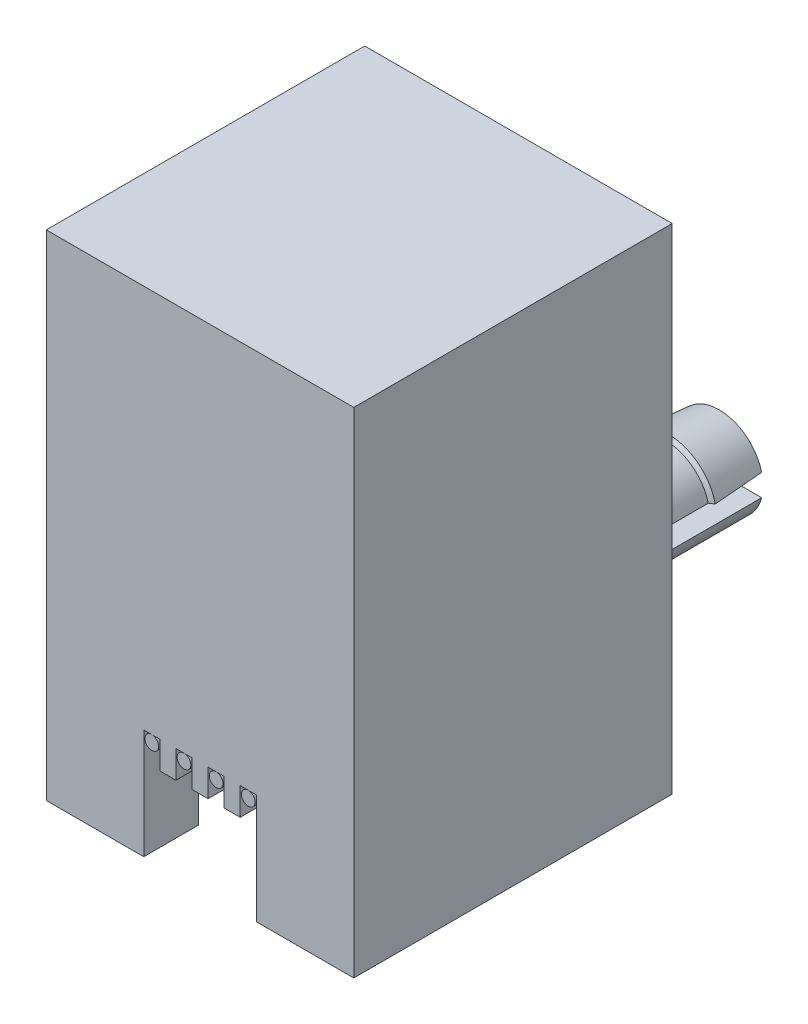
SolidWorks part; units mm, degrees
material "ABS PC"
ref_plane "Front Plane" through (0, 0, 0) normal (0, 0, 1) x (1, 0, 0)
ref_plane "Top Plane" through (0, 0, 0) normal (0, 1, 0) x (1, 0, 0)
ref_plane "Right Plane" through (0, 0, 0) normal (1, 0, 0) x (0, 0, -1)
sketch "Sketch1" plane through (0, 0, 0) normal (0, 1, 0) x (1, 0, 0)
  line L0 (5.6, -5.8) -> (5.6, 5.8)
  line L1 (-5.6, -5.8) -> (5.6, -5.8)
  line L2 (-5.6, -5.8) -> (-5.6, 5.8)
  line L3 (5.6, 5.8) -> (-5.6, 5.8)
  line L4 (-5.6, 0) -> (5.6, 0) construction
  line L5 (0, 5.8) -> (0, -5.8) construction
  dimension "D1" = 11.2
  dimension "D2" = 11.6
extrude "Extrude1" add sketch "Sketch1" along normal mid plane 18
sketch "Sketch2" plane through (0, -9, 0) normal (0, -1, 0) x (1, 0, 0)
  line L0 (-5.6, 5.8) -> (5.6, 5.8) construction
  line L1 (4, 3.8) -> (-4, 3.8)
  line L2 (4, -3) -> (4, 3.8)
  line L3 (4, -3) -> (2.9, -3)
  line L4 (2.9, -4.8) -> (2.9, -3)
  line L5 (2.9, -4.8) -> (-2.9, -4.8)
  line L6 (5.6, -5.8) -> (-5.6, -5.8) construction
  line L7 (0, -5.8) -> (0, 5.8) construction
  line L11 (-2.9, -4.8) -> (-2.9, -3)
  line L12 (-4, -3) -> (-2.9, -3)
  line L13 (-4, -3) -> (-4, 3.8)
  dimension "D1" = 2
  dimension "D2" = 8
  dimension "D4" = 6.8
  dimension "D5" = 1.1
  dimension "D6" = 1.8
extrude "Cut-Extrude1" cut sketch "Sketch2" against normal blind 10
sketch "Sketch3" plane through (0, 0, 5.8) normal (0, 0, 1) x (1, 0, 0)
  line L0 (-2.05, -9) -> (-2.05, -6)
  line L1 (-2.05, -6) -> (2.05, -6)
  line L2 (2.05, -6) -> (2.05, -9)
  line L3 (2.05, -9) -> (-2.05, -9)
  line L4 (0, -9) -> (0, -6) construction
  line L5 (-5.6, -9) -> (5.6, -9) construction
  dimension "D1" = 4.1
  dimension "D2" = 3
extrude "Cut-Extrude2" cut sketch "Sketch3" against normal up to surface (2 mm away) up to face at (0, -4, 3.8)
sketch "Sketch4" plane through (0, 0, -5.8) normal (0, 0, -1) x (-1, 0, 0)
  line L0 (1.5, -7.2) -> (1.5, -9)
  line L1 (2.9, -7.2) -> (1.5, -7.2)
  line L2 (2.9, -4.2) -> (2.9, -7.2)
  line L3 (-2.9, -4.2) -> (2.9, -4.2)
  line L4 (-2.9, -7.2) -> (-2.9, -4.2)
  line L5 (-1.5, -7.2) -> (-2.9, -7.2)
  line L6 (-1.5, -9) -> (-1.5, -7.2)
  line L7 (1.5, -9) -> (-1.5, -9)
  line L8 (0, -9) -> (0, -4.2) construction
  line L9 (-5.6, -9) -> (5.6, -9) construction
  dimension "D1" = 5.8
  dimension "D2" = 3
  dimension "D3" = 1.8
  dimension "D4" = 3
extrude "Cut-Extrude3" cut sketch "Sketch4" against normal up to surface (1 mm away) up to face at (0, -4, -4.8)
sketch "Sketch5" plane through (0, 0, -5.8) normal (0, 0, -1) x (-1, 0, 0)
  line L4 (-5.6, -9) -> (-1.5, -9) construction
  line L5 (-5.6, 9) -> (-5.6, -9) construction
  line L6 (-5.41, -1.12) -> (-2.21, -1.12) construction
  line L7 (-5.3592, -1.52) -> (-2.2608, -1.52)
  line L8 (-5.3592, -0.72) -> (-2.2608, -0.72)
  line L9 (-5.41, -0.72) -> (-2.21, -0.72) construction
  line L10 (-5.41, -1.52) -> (-2.21, -1.52) construction
  arc A1 (-5.3592, -1.52) -> (-2.2608, -1.52) centre (-3.81, -1.12) ccw
  arc A2 (-2.2608, -0.72) -> (-5.3592, -0.72) centre (-3.81, -1.12) ccw
  dimension "D2" = 3.2
  dimension "D3" = 7.88
  dimension "D5" = 1.79
  dimension "D6" = 0.4
  dimension "D7" = 0.4
extrude "Extrude2" add sketch "Sketch5" along normal blind 3.5
ref_plane "Plane1" through (0, 0, -7.4537) normal (0, 0, -1) x (-1, 0, 0)
sketch "Sketch6" plane through (0, 0, -7.4537) normal (0, 0, -1) x (-1, 0, 0)
  line L1 (-5.3592, -0.72) -> (-2.2608, -0.72) construction
  line L2 (-5.5137, -0.72) -> (-2.1063, -0.72)
  arc A0 (-2.1063, -0.72) -> (-5.5137, -0.72) centre (-3.81, -1.12) ccw
  arc A1 (-2.2608, -0.72) -> (-5.3592, -0.72) centre (-3.81, -1.12) ccw construction
  dimension "D1" = 3.5
ref_plane "Plane2" through (0, 0, -7.3537) normal (0, 0, -1) x (-1, 0, 0)
sketch "Sketch7" plane through (0, 0, -7.3537) normal (0, 0, -1) x (-1, 0, 0)
  line L0 (-5.3592, -0.72) -> (-2.2608, -0.72) construction
  line L1 (-5.3592, -0.72) -> (-2.2608, -0.72)
  arc A0 (-2.2608, -0.72) -> (-5.3592, -0.72) centre (-3.81, -1.12) ccw construction
  arc A1 (-2.2608, -0.72) -> (-5.3592, -0.72) centre (-3.81, -1.12) ccw
sketch "Sketch8" plane through (0, 0, -9.3) normal (0, 0, -1) x (-1, 0, 0)
  line L0 (-5.3592, -0.72) -> (-2.2608, -0.72) construction
  line L1 (-5.3592, -0.72) -> (-2.2608, -0.72)
  arc A0 (-2.2608, -0.72) -> (-5.3592, -0.72) centre (-3.81, -1.12) ccw construction
  arc A1 (-2.2608, -0.72) -> (-5.3592, -0.72) centre (-3.81, -1.12) ccw
loft "Loft1" add profiles "Sketch8", "Sketch6" start constraint default connector at (5.3592, -0.72, -9.3) connector at (5.5137, -0.72, -7.4537)
loft "Loft2" add profiles "Sketch6<2>", "Sketch7" connector at (2.1063, -0.72, -7.4537) connector at (2.2608, -0.72, -7.3537)
sketch "Sketch6<2>" plane through (0, 0, -7.4537) normal (0, 0, -1) x (-1, 0, 0) same geometry as "Sketch6"
mirror "Mirror1" about plane through (0, 0, 0) normal (1, 0, 0) of "Extrude2", "Loft1", "Loft2"
sketch "Sketch9" plane through (0, 0, 3.8) normal (0, 0, -1) x (-1, 0, 0)
  line L0 (2.05, -6) -> (-2.05, -6) construction
  line L1 (2.05, -6) -> (1.4643, -6)
  line L2 (2.05, -6) -> (2.05, -5)
  line L3 (2.05, -5) -> (1.4643, -5)
  line L4 (1.4643, -6) -> (1.4643, -5)
  line L5 (-2.05, -6) -> (-1.4643, -6)
  line L6 (-2.05, -6) -> (-2.05, -5)
  line L7 (-2.05, -5) -> (-1.4643, -5)
  line L8 (-1.4643, -6) -> (-1.4643, -5)
  line L9 (0.8786, -6) -> (0.2929, -6)
  line L10 (0.8786, -6) -> (0.8786, -5)
  line L11 (0.8786, -5) -> (0.2929, -5)
  line L12 (0.2929, -6) -> (0.2929, -5)
  line L13 (2.05, -5.5) -> (1.4643, -5.5) construction
  line L14 (-0.2929, -6) -> (-0.8786, -6)
  line L15 (-0.2929, -6) -> (-0.2929, -5)
  line L16 (-0.2929, -5) -> (-0.8786, -5)
  line L17 (-0.8786, -6) -> (-0.8786, -5)
  line L18 (1.4643, -5.5) -> (0.8786, -5.5) construction
  line L19 (0.8786, -5.5) -> (0.2929, -5.5) construction
  line L20 (0.2929, -5.5) -> (-0.2929, -5.5) construction
  line L21 (-0.2929, -5.5) -> (-0.8786, -5.5) construction
  line L22 (-0.8786, -5.5) -> (-1.4643, -5.5) construction
  line L23 (-1.4643, -5.5) -> (-2.05, -5.5) construction
  dimension "D1" = 1
extrude "Cut-Extrude4" cut sketch "Sketch9" against normal up to surface (2 mm away) up to face at (0, -3.75, 5.8)
sketch "Sketch10" plane through (0, 1, 0) normal (0, -1, 0) x (1, 0, 0)
  line L2 (-2.4, -3) -> (-2.4, -4.8)
  line L3 (-2.4, -3) -> (-2.4, -4.8) construction
  line L5 (2.4, -4.8) -> (2.4, -3)
  line L6 (2.4, -4.8) -> (2.4, -3) construction
  line L7 (-2.4, 0) -> (-2.4, -4.3)
  line L8 (-2.9, -4.3) -> (2.9, -4.3)
  line L9 (-2.9, -4.3) -> (2.9, -4.3) construction
  line L10 (-2.4, -4.3) -> (2.4, -4.3)
  line L11 (2.4, -4.3) -> (2.4, 0)
  line L12 (2.4, 0) -> (-2.4, 0)
  dimension "D1" = 0.5
  dimension "D2" = 0.5
  dimension "D3" = 0.5
extrude "Cut-Extrude5" cut sketch "Sketch10" against normal blind 0.3
sketch "Sketch11" plane through (0, 1, 0) normal (0, -1, 0) x (1, 0, 0)
  line L0 (-2.05, 3.8) -> (-1.4643, 3.8) construction
  line L1 (-2.05, 3.8) -> (-1.4643, 3.8)
  line L2 (-0.8786, 3.8) -> (-0.2929, 3.8) construction
  line L3 (-0.8786, 3.8) -> (-0.2929, 3.8)
  line L4 (0.2929, 3.8) -> (0.8786, 3.8) construction
  line L5 (0.2929, 3.8) -> (0.8786, 3.8)
  line L6 (1.4643, 3.8) -> (2.05, 3.8) construction
  line L7 (1.4643, 3.8) -> (2.05, 3.8)
  line L8 (-2.4, -2.15) -> (2.4, -2.15) construction
  line L9 (-2.4, 0) -> (-2.4, -4.3) construction
  line L10 (2.4, -4.3) -> (2.4, 0) construction
  line L11 (-2.05, 3.8) -> (-2.05, -2.15)
  line L12 (-2.05, -2.15) -> (-1.4643, -2.15)
  line L13 (-1.4643, -2.15) -> (-1.4643, 3.8)
  line L14 (-0.8786, 3.8) -> (-0.8786, -2.15)
  line L15 (-0.8786, -2.15) -> (-0.2929, -2.15)
  line L16 (-0.2929, -2.15) -> (-0.2929, 3.8)
  line L17 (0.2929, 3.8) -> (0.2929, -2.15)
  line L18 (0.2929, -2.15) -> (0.8786, -2.15)
  line L19 (0.8786, -2.15) -> (0.8786, 3.8)
  line L20 (1.4643, 3.8) -> (1.4643, -2.15)
  line L21 (1.4643, -2.15) -> (2.05, -2.15)
  line L22 (2.05, -2.15) -> (2.05, 3.8)
extrude "Cut-Extrude6" cut sketch "Sketch11" against normal blind 0.6
ref_plane "Plane3" through (-1.7571, 0, 0) normal (1, 0, 0) x (0, 0, -1)
sketch "Sketch12" plane through (-1.7571, 0, 0) normal (1, 0, 0) x (0, 0, -1)
  line L0 (-5.8, -5) -> (-4.2195, -5)
  line L1 (-3.7271, -4.5868) -> (-2.6362, 1.6)
  line L2 (-5.8, -5) -> (-3.8, -5) construction
  line L3 (-5.8, -5) -> (-5.8, -9) construction
  line L4 (-3.8, 1.6) -> (2.15, 1.6) construction
  arc A0 (-4.2195, -5) -> (-3.7271, -4.5868) centre (-4.2195, -4.5) ccw
  point P12 (-3.8, -5)
  dimension "D3" = 0.5
  dimension "D1" = 2
  dimension "D2" = 100
sketch "Sketch13" plane through (0, 0, 5.8) normal (0, 0, 1) x (1, 0, 0)
  line L0 (-1.4643, -5) -> (-2.05, -5) construction
  circle A0 centre (-1.7571, -5.25) radius 0.25
  point P4 (-1.7571, -5)
  dimension "D1" = 0.5
sweep "Sweep1" add profiles "Sketch13" path "Sketch12"
pattern_linear "LPattern2" count 4 spacing 1.1714 along (1, 0, 0) of bodies 112
ref_plane "Plane4" through (0, 0, 0.4) normal (0, 0, -1) x (-1, 0, 0)
sketch "Sketch14" plane through (0, 0, 0.4) normal (0, 0, -1) x (-1, 0, 0)
  line L0 (0, 0) -> (0, -20) construction
  dimension "D1" = 20
ref_axis "Axis1" through (0, -20, 0.4) along (0, 1, 0)
